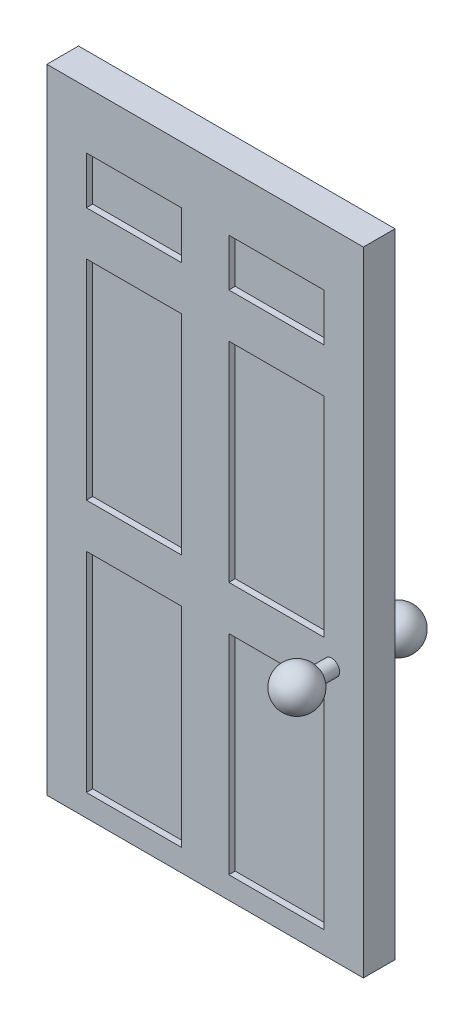
SolidWorks part; units mm, degrees
ref_plane "Front Plane" through (0, 0, 0) normal (0, 0, 1) x (1, 0, 0)
ref_plane "Top Plane" through (0, 0, 0) normal (0, 1, 0) x (1, 0, 0)
ref_plane "Right Plane" through (0, 0, 0) normal (1, 0, 0) x (0, 0, -1)
sketch "Sketch1" plane through (0, 0, 0) normal (0, 0, 1) x (1, 0, 0)
  line L1 (-25, 50) -> (25, 50)
  line L2 (-25, 50) -> (-25, -50)
  line L3 (-25, -50) -> (25, -50)
  line L4 (25, 50) -> (25, -50)
  line L5 (-25, 50) -> (25, -50) construction
  line L6 (-25, -50) -> (25, 50) construction
  point P0 (0, 0)
  dimension "D1" = 50
  dimension "D2" = 100
extrude "Boss-Extrude1" add sketch "Sketch1" along normal mid plane 5
sketch "Sketch2" plane through (0, 0, 2.5) normal (0, 0, 1) x (1, 0, 0)
  line L0 (-25, -50) -> (25, -50) construction
  line L1 (25, -50) -> (25, 50) construction
  circle A0 centre (20, -10) radius 1.25
  dimension "D3" = 2.5
  dimension "D1" = 40
  dimension "D2" = 5
extrude "Boss-Extrude2" add sketch "Sketch2" along normal blind 2.5
ref_plane "Plane1" through (20, 0, 0) normal (1, 0, 0) x (0, 0, -1)
sketch "Sketch3" plane through (20, 0, 0) normal (1, 0, 0) x (0, 0, -1)
  line L0 (-5, -8.75) -> (-5, -11.25) construction
  line L1 (-8, -6.75) -> (-8, -13.25)
  arc A0 (-8, -6.75) -> (-8, -13.25) centre (-8, -10) ccw
  point P5 (-10.5, -18.807)
  point P6 (0, 0)
  dimension "D1" = 3.25
  dimension "D2" = 3
  dimension "D3" = 40
revolve "Revolve1" add sketch "Sketch3" angle 360 about L1
sketch "Sketch4" plane through (0, 0, 2.5) normal (0, 0, 1) x (1, 0, 0)
  line L0 (3.75, 0) -> (-3.75, 0) construction
  line L1 (-3.75, 41) -> (-18.75, 41)
  line L2 (-3.75, 41) -> (-3.75, 33.5)
  line L3 (-3.75, 33.5) -> (-18.75, 33.5)
  line L4 (-18.75, 41) -> (-18.75, 33.5)
  line L5 (3.75, 41) -> (18.75, 41)
  line L6 (3.75, 41) -> (3.75, 33.5)
  line L7 (3.75, 33.5) -> (18.75, 33.5)
  line L8 (18.75, 41) -> (18.75, 33.5)
  line L9 (3.75, 26.5) -> (18.75, 26.5)
  line L10 (3.75, 26.5) -> (3.75, -6.5)
  line L11 (3.75, -6.5) -> (18.75, -6.5)
  line L12 (18.75, 26.5) -> (18.75, -6.5)
  line L13 (-3.75, 26.5) -> (-18.75, 26.5)
  line L14 (-3.75, 26.5) -> (-3.75, -6.5)
  line L15 (-3.75, -6.5) -> (-18.75, -6.5)
  line L16 (-18.75, 26.5) -> (-18.75, -6.5)
  line L17 (-3.75, -13.5) -> (-18.75, -13.5)
  line L18 (-3.75, -13.5) -> (-3.75, -46.5)
  line L19 (-3.75, -46.5) -> (-18.75, -46.5)
  line L20 (-18.75, -13.5) -> (-18.75, -46.5)
  line L21 (3.75, -13.5) -> (18.75, -13.5)
  line L22 (3.75, -13.5) -> (3.75, -46.5)
  line L23 (3.75, -46.5) -> (18.75, -46.5)
  line L24 (18.75, -13.5) -> (18.75, -46.5)
  line L25 (-25, -50) -> (25, -50) construction
  point P28 (0, 0)
  dimension "D1" = 7.5
  dimension "D2" = 15
  dimension "D3" = 7
  dimension "D4" = 33
  dimension "D5" = 7
  dimension "D6" = 7.5
  dimension "D7" = 3.5
extrude "Cut-Extrude1" cut sketch "Sketch4" against normal blind 1
mirror "Mirror1" about plane through (0, 0, 0) normal (0, 0, 1) of "Boss-Extrude2", "Revolve1", "Cut-Extrude1"
